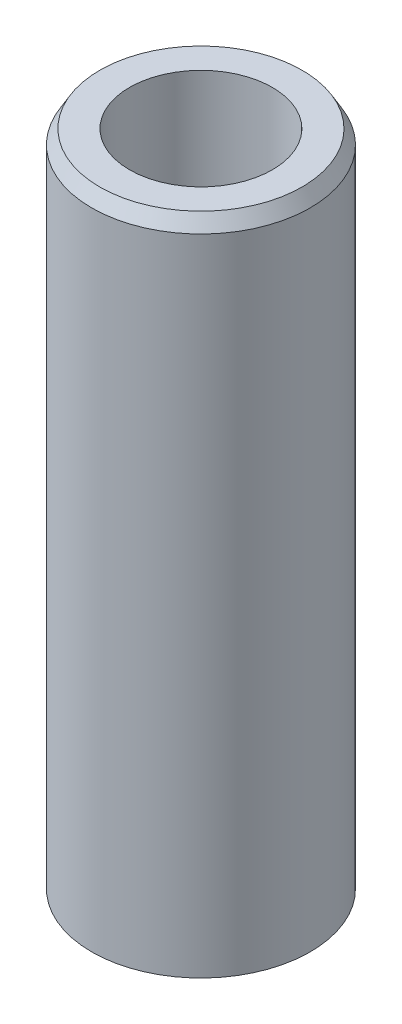
SolidWorks part; units mm, degrees
ref_plane "Front Plane" through (0, 0, 0) normal (0, 0, 1) x (1, 0, 0)
ref_plane "Top Plane" through (0, 0, 0) normal (0, 1, 0) x (1, 0, 0)
ref_plane "Right Plane" through (0, 0, 0) normal (1, 0, 0) x (0, 0, -1)
sketch "Sketch1" plane through (0, 0, 0) normal (0, 1, 0) x (1, 0, 0)
  circle A0 centre (0, 0) radius 35
  dimension "SHAFT_OD" = 70
extrude "Boss-Extrude1" add sketch "Sketch1" along normal blind 213.4682
sketch "Sketch2" plane through (0, 0, 0) normal (0, 1, 0) x (1, 0, 0)
  circle A0 centre (0, 0) radius 22.8745
  dimension "BORE_D" = 45.7489
extrude "Cut-Extrude1" cut sketch "Sketch2" along normal through all
chamfer "Chamfer1" distance 4.495 angle 30 2 edges at (0, 213.4682, 35) (0, 0, 35) first distance on face at (0, 213.4682, 35) first distance on face at (0, 0, 22.8745)
